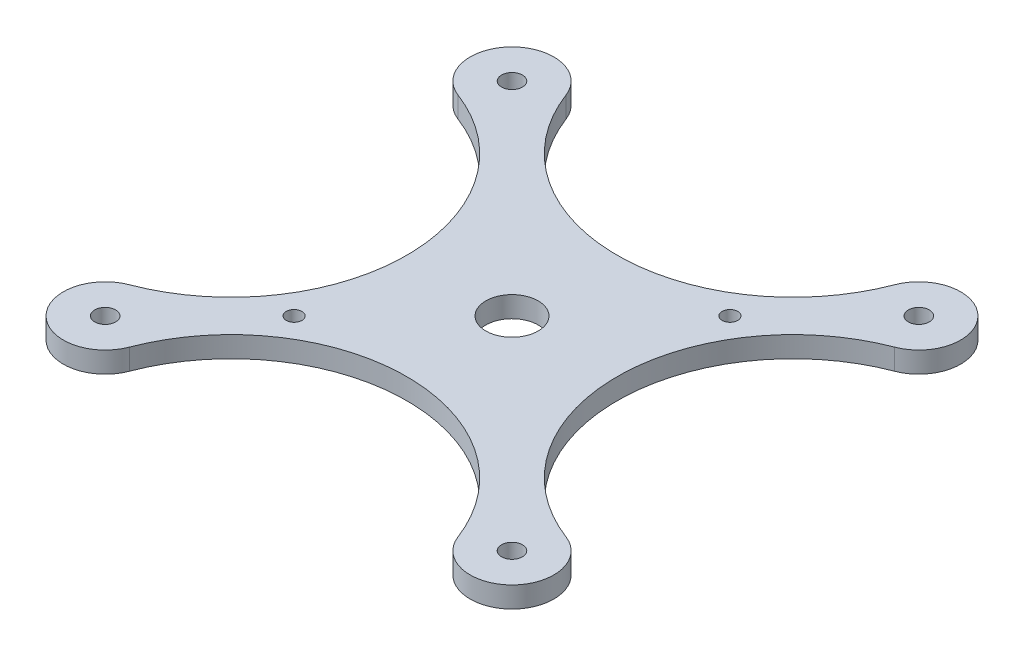
SolidWorks part; units mm, degrees
material "PET"
ref_plane "Front Plane" through (0, 0, 0) normal (0, 0, 1) x (1, 0, 0)
ref_plane "Top Plane" through (0, 0, 0) normal (0, 1, 0) x (1, 0, 0)
ref_plane "Right Plane" through (0, 0, 0) normal (1, 0, 0) x (0, 0, -1)
sketch "Sketch1" plane through (0, 0, 0) normal (0, 1, 0) x (1, 0, 0)
  line L17 (0, 20.1) -> (0, -20.1) construction
  line L22 (-38.8909, 38.8909) -> (38.8909, -38.8909) construction
  line L29 (0, -2.2) -> (0, 2.2) construction
  line L31 (38.8909, 38.8909) -> (-38.8909, -38.8909) construction
  line L36 (-2.2, 0) -> (2.2, 0) construction
  circle A8 centre (0, 0) radius 55 construction
  circle A9 centre (-38.8909, 38.8909) radius 2
  circle A10 centre (38.8909, 38.8909) radius 2
  circle A11 centre (38.8909, -38.8909) radius 2
  circle A12 centre (-38.8909, -38.8909) radius 2
  arc A13 (-31.4161, 41.7417) -> (31.4161, 41.7417) centre (0, 53.7233) ccw
  arc A14 (41.7417, 31.4161) -> (41.7417, -31.4161) centre (53.7233, 0) ccw
  arc A15 (31.4161, -41.7417) -> (-31.4161, -41.7417) centre (0, -53.7233) ccw
  arc A16 (-41.7417, -31.4161) -> (-41.7417, 31.4161) centre (-53.7233, 0) ccw
  arc A17 (-31.4161, 41.7417) -> (-41.7417, 31.4161) centre (-38.8909, 38.8909) ccw
  arc A18 (41.7417, 31.4161) -> (31.4161, 41.7417) centre (38.8909, 38.8909) ccw
  arc A19 (31.4161, -41.7417) -> (41.7417, -31.4161) centre (38.8909, -38.8909) ccw
  arc A20 (-41.7417, -31.4161) -> (-31.4161, -41.7417) centre (-38.8909, -38.8909) ccw
  circle A21 centre (0, 0) radius 5
  circle A22 centre (20.8314, 20.8314) radius 1.5
  circle A23 centre (-20.8314, -20.8314) radius 1.5
  point P6 (0, 0)
  point P29 (0, 0)
  point P30 (38.8909, 38.8909)
  point P32 (41.7417, 31.4161)
  point P33 (41.7417, 31.4161)
  point P34 (0, 0)
  dimension "D1" = 4
  dimension "D2" = 110
  dimension "D3" = 8
  dimension "D4" = 40.2
  dimension "D5" = 10
  dimension "D7" = 3
  dimension "D6" = 58.92
extrude "Boss-Extrude1" add sketch "Sketch1" along normal blind 4
